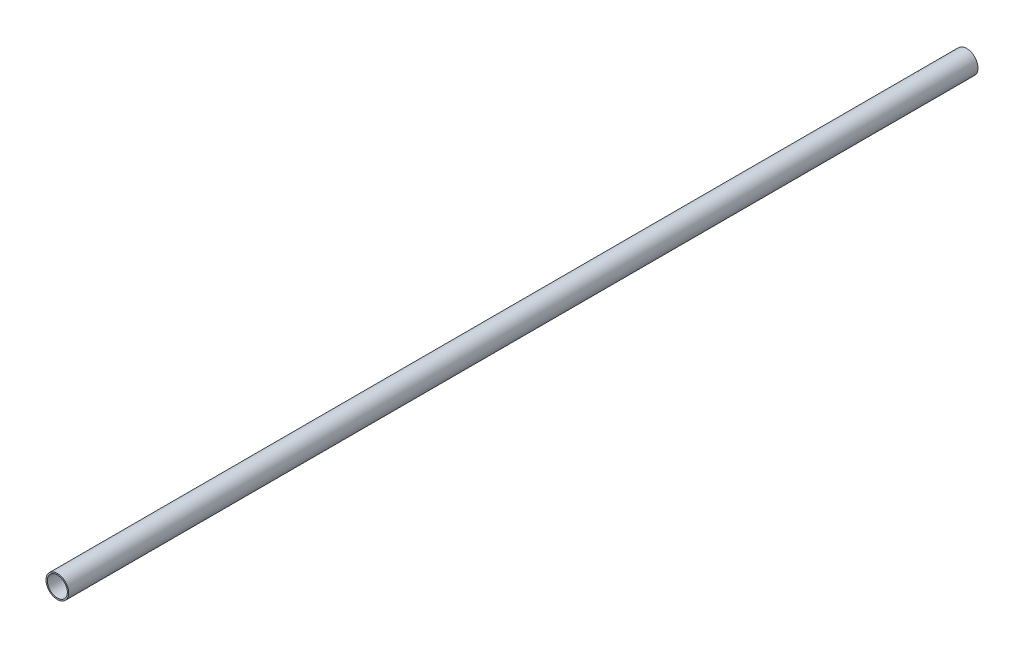
SolidWorks part; units mm, degrees
ref_plane "Front Plane" through (0, 0, 0) normal (0, 0, 1) x (1, 0, 0)
ref_plane "Top Plane" through (0, 0, 0) normal (0, 1, 0) x (1, 0, 0)
ref_plane "Right Plane" through (0, 0, 0) normal (1, 0, 0) x (0, 0, -1)
sketch "Sketch1" plane through (0, 0, 0) normal (0, 0, 1) x (1, 0, 0)
  circle A1 centre (0, 0) radius 12.5
  circle A2 centre (0, 0) radius 11
  dimension "D1" = 25
  dimension "D2" = 22
extrude "Boss-Extrude1" add sketch "Sketch1" along normal blind 500 and the other way blind 500
